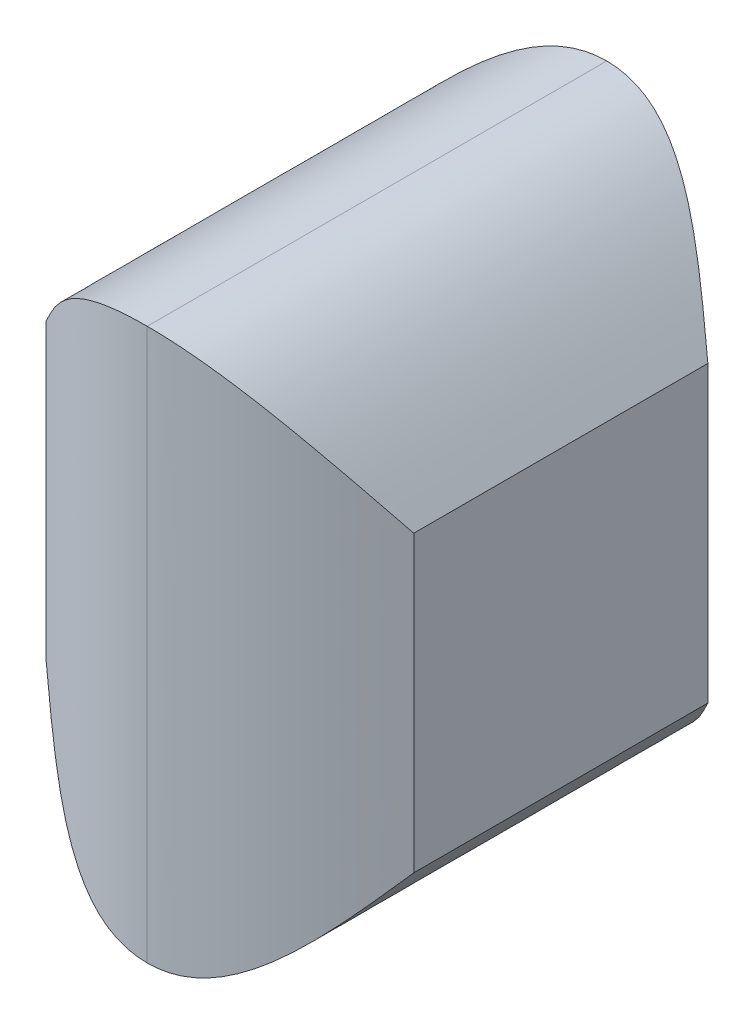
SolidWorks part; units mm, degrees
ref_plane "Front Plane" through (0, 0, 0) normal (0, 0, 1) x (1, 0, 0)
ref_plane "Top Plane" through (0, 0, 0) normal (0, 1, 0) x (1, 0, 0)
ref_plane "Right Plane" through (0, 0, 0) normal (1, 0, 0) x (0, 0, -1)
sketch "Sketch1" plane through (300, 0, 0) normal (1, 0, 0) x (0, 0, -1)
  line L0 (22.5, 75) -> (102.5, 75) construction
  line L1 (125, 0) -> (125, 150) construction
  line L3 (62.5, 35) -> (62.5, 115) construction
  line L4 (0, 150) -> (0, 0) construction
  line L5 (0, 0) -> (125, 0) construction
  line L6 (125, 150) -> (0, 150) construction
  line L8 (22.5, 115) -> (22.5, 35)
  line L9 (22.5, 35) -> (102.5, 35)
  line L10 (102.5, 35) -> (102.5, 115)
  line L11 (102.5, 115) -> (22.5, 115)
  dimension "D1" = 80
  dimension "D2" = 80
ref_plane "Plane1" through (350, 0, 0) normal (1, 0, 0) x (0, 0, -1)
sketch "Sketch2" plane through (350, 0, 0) normal (1, 0, 0) x (0, 0, -1)
  line L4 (0, 150) -> (0, 0) construction
  line L5 (0, 0) -> (125, 0) construction
  line L6 (125, 150) -> (0, 150) construction
  line L7 (125, 0) -> (125, 150) construction
  line L8 (0, 150) -> (0, 0)
  line L9 (0, 0) -> (125, 0)
  line L10 (125, 0) -> (125, 150)
  line L11 (125, 150) -> (0, 150)
loft "Loft1" add profiles "Sketch1", "Sketch2" end constraint normal to profile end tangent length 1 connector at (300, 115, -102.5) connector at (350, 150, -125)
mirror "Mirror1" about plane through (350, 0, 0) normal (1, 0, 0) of "Loft1"
